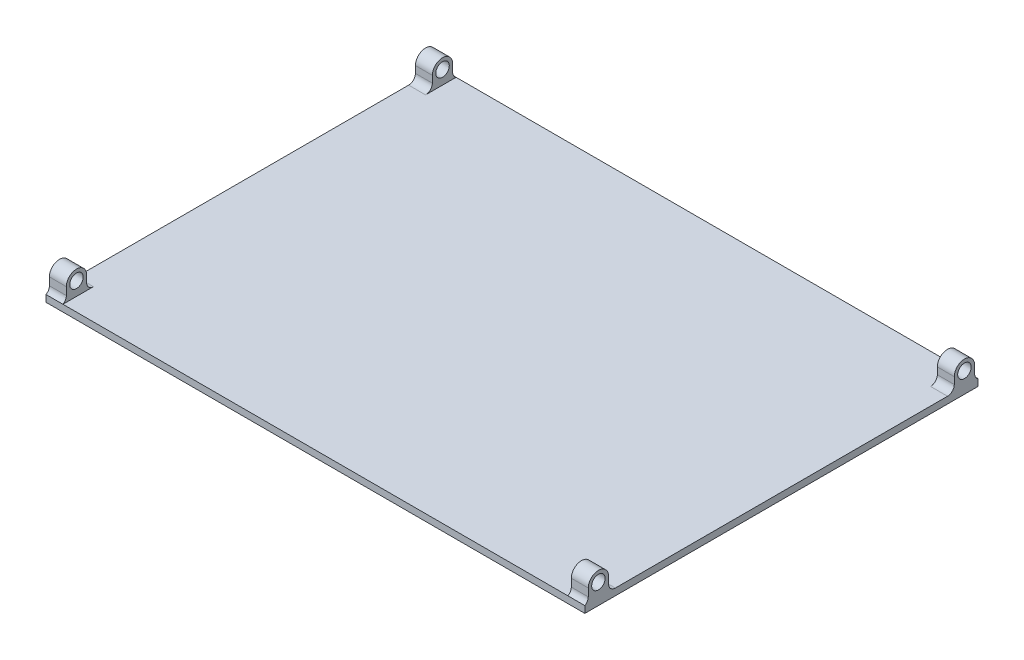
SolidWorks part; units mm, degrees
ref_plane "前视基准面" through (0, 0, 0) normal (0, 0, 1) x (1, 0, 0)
ref_plane "上视基准面" through (0, 0, 0) normal (0, 1, 0) x (1, 0, 0)
ref_plane "右视基准面" through (0, 0, 0) normal (1, 0, 0) x (0, 0, -1)
sketch "草图1" plane through (0, 0, 0) normal (0, 1, 0) x (1, 0, 0)
  line L1 (-79.5, 58) -> (79.5, 58)
  line L2 (-79.5, 58) -> (-79.5, -58)
  line L3 (-79.5, -58) -> (79.5, -58)
  line L4 (79.5, 58) -> (79.5, -58)
  line L5 (-79.5, 58) -> (79.5, -58) construction
  line L6 (-79.5, -58) -> (79.5, 58) construction
  point P0 (0, 0)
  dimension "D1" = 159
  dimension "D2" = 116
extrude "凸台-拉伸1" add sketch "草图1" along normal blind 2
sketch "草图3" plane through (0, 0, 0) normal (1, 0, 0) x (0, 0, -1)
  line L0 (0, -4.1306) -> (0, 6) construction
  line L1 (54, 6) -> (-54, 6) construction
  line L2 (-58, 2) -> (-58, 6) construction
  line L3 (-58, 6) -> (-54, 6) construction
  line L4 (-54, 6) -> (-54, 2) construction
  line L5 (-58, 2) -> (58, 2) construction
  line L6 (-57, 6) -> (-57, 2)
  line L7 (-57, 2) -> (-51, 2)
  line L8 (-51, 2) -> (-51, 6)
  line L9 (0, 6) -> (47.2011, 6) construction
  line L10 (47.2011, 6) -> (58, 6) construction
  line L11 (58, 6) -> (58, 2) construction
  line L12 (54, 6) -> (54, 2) construction
  line L13 (58, 6) -> (54, 6) construction
  line L14 (51, 2) -> (51, 6)
  line L15 (57, 2) -> (51, 2)
  line L16 (57, 6) -> (57, 2)
  arc A0 (-51, 6) -> (-57, 6) centre (-54, 6) ccw
  circle A1 centre (-54, 6) radius 1.99
  circle A2 centre (54, 6) radius 1.99
  arc A3 (51, 6) -> (57, 6) centre (54, 6) cw
  dimension "D3" = 3
  dimension "D4" = 3.98
  dimension "D1" = 4
  dimension "D2" = 4
extrude "凸台-拉伸3" add sketch "草图3" along normal mid plane 159
sketch "草图4" plane through (0, 0, 0) normal (0, 0, 1) x (1, 0, 0)
  line L0 (79.5, 9) -> (-79.5, 9) construction
  line L1 (-74.5, 9) -> (74.5, 9)
  line L2 (-74.5, 9) -> (-74.5, 2)
  line L3 (-74.5, 2) -> (74.5, 2)
  line L4 (74.5, 9) -> (74.5, 2)
  line L5 (-79.5, 2) -> (79.5, 2) construction
  line L6 (-79.5, 9) -> (-79.5, 6) construction
  line L7 (79.5, 6) -> (79.5, 9) construction
  dimension "D1" = 5
  dimension "D2" = 5
extrude "切除-拉伸2" cut sketch "草图4" against normal mid plane 159
fillet "圆角3" radius 2 8 edges at (77, 2, 57) (77, 2, 51) (77, 2, -51) (77, 2, -57) (-77, 2, 51) (-77, 2, 57) (-77, 2, -51) (-77, 2, -57)
